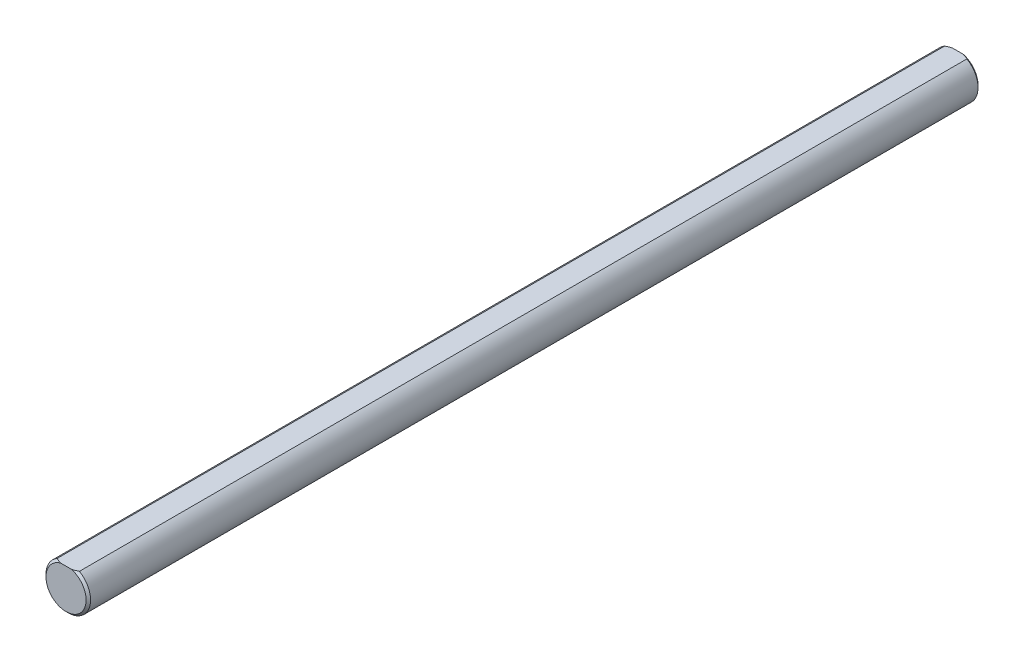
SolidWorks part; units mm, degrees
ref_plane "Front Plane" through (0, 0, 0) normal (0, 0, 1) x (1, 0, 0)
ref_plane "Top Plane" through (0, 0, 0) normal (0, 1, 0) x (1, 0, 0)
ref_plane "Right Plane" through (0, 0, 0) normal (1, 0, 0) x (0, 0, -1)
sketch "Sketch1" plane through (0, 0, 0) normal (0, 0, 1) x (1, 0, 0)
  line L0 (2.5, 4.3301) -> (-2.5, 4.3301) construction
  line L1 (0, 4.3301) -> (0, 0) construction
  line L2 (0, 0) -> (0, -5) construction
  circle A1 centre (0, 0) radius 5 construction
  dimension "Diameter" = 10
  dimension "Flat Width" = 5
  dimension "D1" = 9.3301
sketch "Sketch2" plane through (0, 0, 0) normal (1, 0, 0) x (0, 0, -1)
  line L0 (-100, 5) -> (100, 5) construction
  line L1 (0, 5) -> (0, -5) construction
  line L2 (0, 5) -> (0, -5) construction
  line L3 (-100, 5) -> (-100, 0) construction
  line L4 (-100, 0) -> (0, 0) construction
  line L6 (-100, 4.5) -> (-99.5, 5) construction
  point P2 (0, 5)
  point P3 (80, 5)
  point P4 (-80, 5)
  dimension "Length/ D-Profile Length" = 200
  dimension "D2" = 20
  dimension "D1" = 20
  dimension "Chamfer Typ." = 45
  dimension "D4" = 0.5
sketch "Sketch3" plane through (0, 0, 0) normal (0, 0, 1) x (1, 0, 0)
  circle A1 centre (0, 0) radius 5 construction
  circle A3 centre (0, 0) radius 5
extrude "Boss-Extrude2" add sketch "Sketch3" along normal up to vertex (100 mm away) and the other way up to vertex (100 mm away) up to point (0, 5, 100) other way up to point (0, 5, -100)
sketch "Sketch10" plane through (0, 0, 0) normal (0, 0, 1) x (1, 0, 0)
  line L0 (-2.5, 4.3301) -> (2.5, 4.3301)
  line L1 (0, 0) -> (0, 5) construction
  circle A0 centre (0, 0) radius 5 construction
  circle A1 centre (0, 0) radius 5 construction
  arc A2 (-2.5, 4.3301) -> (2.5, 4.3301) centre (0, 0) cw
extrude "Cut-Extrude5" cut sketch "Sketch10" against normal through all both and the other way through all
chamfer "Chamfer1" distance 0.5 angle 45 2 edges at (0, -5, 100) (0, -5, -100)
equation "\"D1@Chamfer1\"= \"Diameter@Sketch1\" / 20"
equation "\"D1@Sketch2\"=\"Diameter@Sketch1\"*2"
equation "\"D2@Sketch2\"=\"D1@Sketch2\""
equation "\"D4@Sketch2\"=\"Diameter@Sketch1\" / 20"
